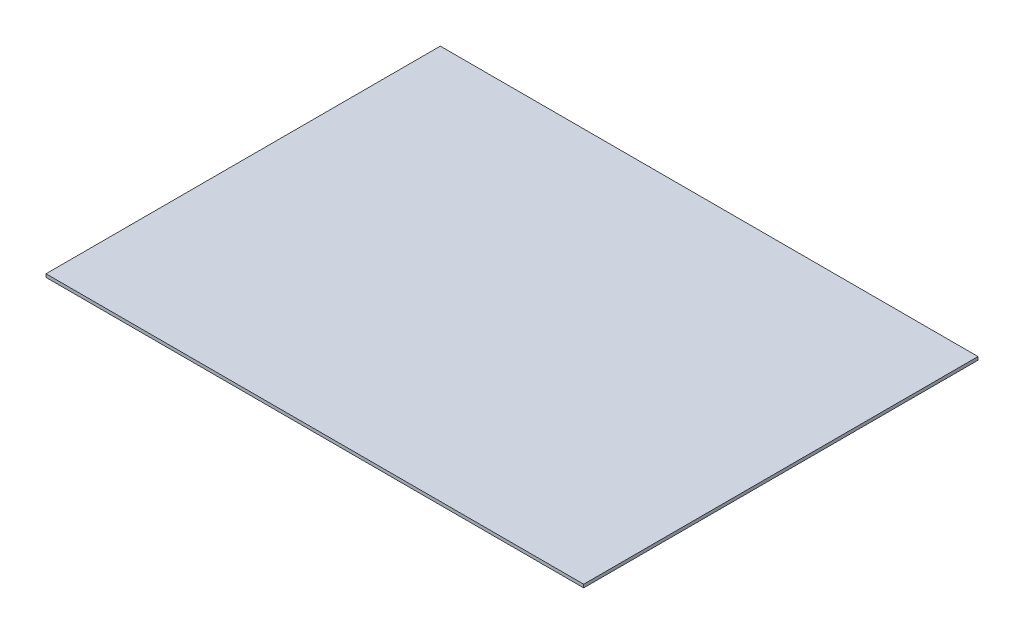
SolidWorks part; units mm, degrees
material "PC High Viscosity"
ref_plane "Front Plane" through (0, 0, 0) normal (0, 0, 1) x (1, 0, 0)
ref_plane "Top Plane" through (0, 0, 0) normal (0, 1, 0) x (1, 0, 0)
ref_plane "Right Plane" through (0, 0, 0) normal (1, 0, 0) x (0, 0, -1)
sketch "Sketch1" plane through (0, 0, 0) normal (0, 1, 0) x (1, 0, 0)
  line L1 (-133.35, 97.79) -> (133.35, 97.79)
  line L2 (-133.35, 97.79) -> (-133.35, -97.79)
  line L3 (-133.35, -97.79) -> (133.35, -97.79)
  line L4 (133.35, 97.79) -> (133.35, -97.79)
  line L5 (-133.35, 97.79) -> (133.35, -97.79) construction
  line L6 (-133.35, -97.79) -> (133.35, 97.79) construction
  point P0 (0, 0)
  dimension "D1" = 266.7
  dimension "D2" = 195.58
extrude "Boss-Extrude1" add sketch "Sketch1" along normal blind 1.5875
